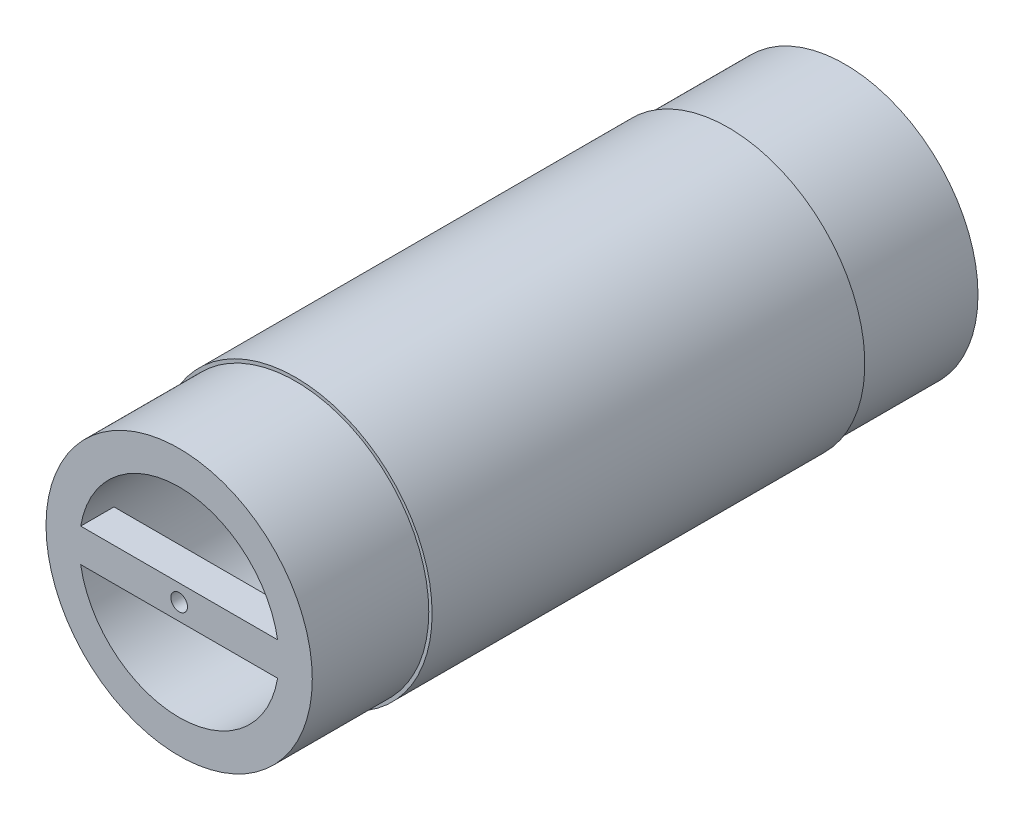
SolidWorks part; units mm, degrees
ref_plane "Front Plane" through (0, 0, 0) normal (0, 0, 1) x (1, 0, 0)
ref_plane "Top Plane" through (0, 0, 0) normal (0, 1, 0) x (1, 0, 0)
ref_plane "Right Plane" through (0, 0, 0) normal (1, 0, 0) x (0, 0, -1)
sketch "Sketch1" plane through (0, 0, 0) normal (0, 0, 1) x (1, 0, 0)
  line L1 (29.5804, 5) -> (-29.5804, 5)
  line L3 (29.5804, -5) -> (-29.5804, -5)
  circle A0 centre (0, 0) radius 40
  arc A1 (-29.5804, -5) -> (29.5804, -5) centre (0, 0) ccw
  arc A2 (29.5804, 5) -> (-29.5804, 5) centre (0, 0) ccw
  dimension "D1" = 80
  dimension "D2" = 10
  dimension "D3" = 10
extrude "Boss-Extrude1" add sketch "Sketch1" along normal mid plane 200
sketch "Sketch2" plane through (0, 0, 100) normal (0, 0, 1) x (1, 0, 0)
  line L0 (-29.5804, 5) -> (29.5804, 5)
  line L1 (29.5804, -5) -> (-29.5804, -5)
  arc A0 (29.5804, -5) -> (29.5804, 5) centre (0, 0) ccw
  arc A1 (-29.5804, 5) -> (-29.5804, -5) centre (0, 0) ccw
extrude "Cut-Extrude1" cut sketch "Sketch2" against normal offset from surface (180 mm away) 10 from offset 10 up to face at (0, 17.5, -100) offset against normal yes
sketch "Sketch3" plane through (0, 0, 100) normal (0, 0, 1) x (1, 0, 0)
  circle A0 centre (0, 0) radius 2.5
  dimension "D1" = 5
extrude "Cut-Extrude2" cut sketch "Sketch3" against normal through all both and the other way through all
sketch "Sketch4" plane through (0, 0, -100) normal (0, 0, -1) x (-1, 0, 0)
  circle A0 centre (0, 0) radius 41
  circle A1 centre (0, 0) radius 40 construction
  circle A2 centre (0, 0) radius 40
  dimension "D1" = 1
extrude "Boss-Extrude2" add sketch "Sketch4" against normal offset from surface (130 mm away) 35 from offset 35 up to face at (2.5, 0, 100) offset against normal yes
scale "Scale1" scale about centroid uniform scaling yes scale factor 1.1
